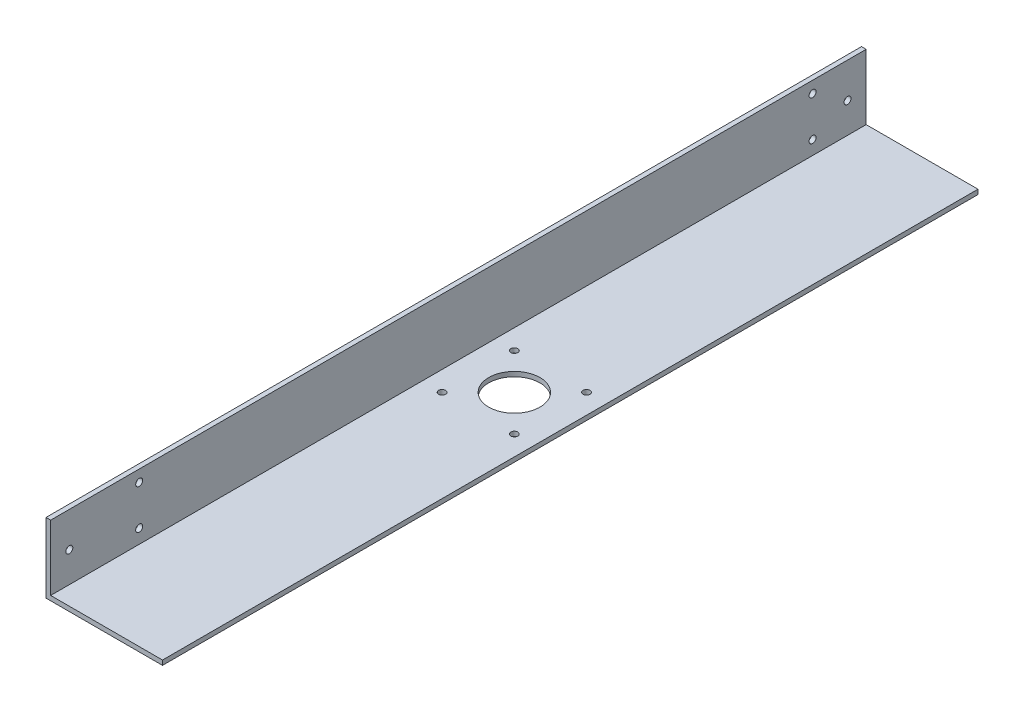
SolidWorks part; units mm, degrees
ref_plane "Front Plane" through (0, 0, 0) normal (0, 0, 1) x (1, 0, 0)
ref_plane "Top Plane" through (0, 0, 0) normal (0, 1, 0) x (1, 0, 0)
ref_plane "Right Plane" through (0, 0, 0) normal (1, 0, 0) x (0, 0, -1)
sketch "Sketch1" plane through (0, 0, 0) normal (0, 0, 1) x (1, 0, 0)
  line L0 (0, 0) -> (0, 30)
  line L1 (0, 30) -> (2, 30)
  line L2 (2, 30) -> (2, 2)
  line L3 (2, 2) -> (50, 2)
  line L4 (50, 2) -> (50, 0)
  line L5 (50, 0) -> (0, 0)
extrude "Boss-Extrude1" add sketch "Sketch1" along normal up to surface (350 mm away)
sketch "Sketch7" plane through (0, 2, 0) normal (0, 1, 0) x (1, 0, 0)
  circle A0 centre (26, -175) radius 11
  point P7 (2, -350)
extrude "Cut-Extrude1" cut sketch "Sketch7" against normal through all from surface starting at face at (26, 2, 175)
sketch "Sketch8" plane through (0, 2, 0) normal (0, 1, 0) x (1, 0, 0)
  circle A0 centre (41.5, -190.5) radius 1.5
  circle A1 centre (41.5, -159.5) radius 1.5
  circle A2 centre (10.5, -190.5) radius 1.5
  circle A3 centre (10.5, -159.5) radius 1.5
extrude "Cut-Extrude2" cut sketch "Sketch8" against normal through all
hole_wizard "Ø3.0 (3) Diameter Hole1" positions "Sketch9" profile "Sketch10" hole size "Ø3.0" standard "ISO"
sketch "Sketch9" plane through (0, 182.32, 128.862) normal (-1, 0, 0) x (0, 0, -1)
  point P0 (105.862, 174.32)
  point P2 (105.862, 157.32)
  point P4 (120.862, 167.32)
sketch "Sketch10" plane through (0, 8, 23) normal (0, 1, 0) x (0, 0, 1)
  line L0 (0, 0) -> (0, 1.999)
  line L1 (0, 1.999) -> (1.5, 1.999)
  line L2 (1.5, 1.999) -> (1.5, 0)
  line L3 (1.5, 0) -> (0, 0)
  line L4 (0, -6.35) -> (0, 107.95) construction
  dimension "Thru Hole Dia." = 3
  dimension "Thru Hole Depth" = 1.999
hole_wizard "Ø3.0mm Dowel Hole1" positions "Sketch13" profile "Sketch14" hole
sketch "Sketch13" plane through (0, 182.32, 128.862) normal (-1, 0, 0) x (0, 0, -1)
  point P0 (-183.138, 157.32)
  point P1 (-213.138, 167.32)
  point P2 (-183.138, 174.32)
sketch "Sketch14" plane through (0, 25, 312) normal (0, 1, 0) x (0, 0, 1)
  line L0 (0, 0) -> (0, 1.999)
  line L1 (0, 1.999) -> (1.5, 1.999)
  line L2 (1.5, 1.999) -> (1.5, 0)
  line L3 (1.5, 0) -> (0, 0)
  line L4 (0, -6.35) -> (0, 107.95) construction
  dimension "Thru Hole Dia." = 3
  dimension "Thru Hole Depth" = 1.999
